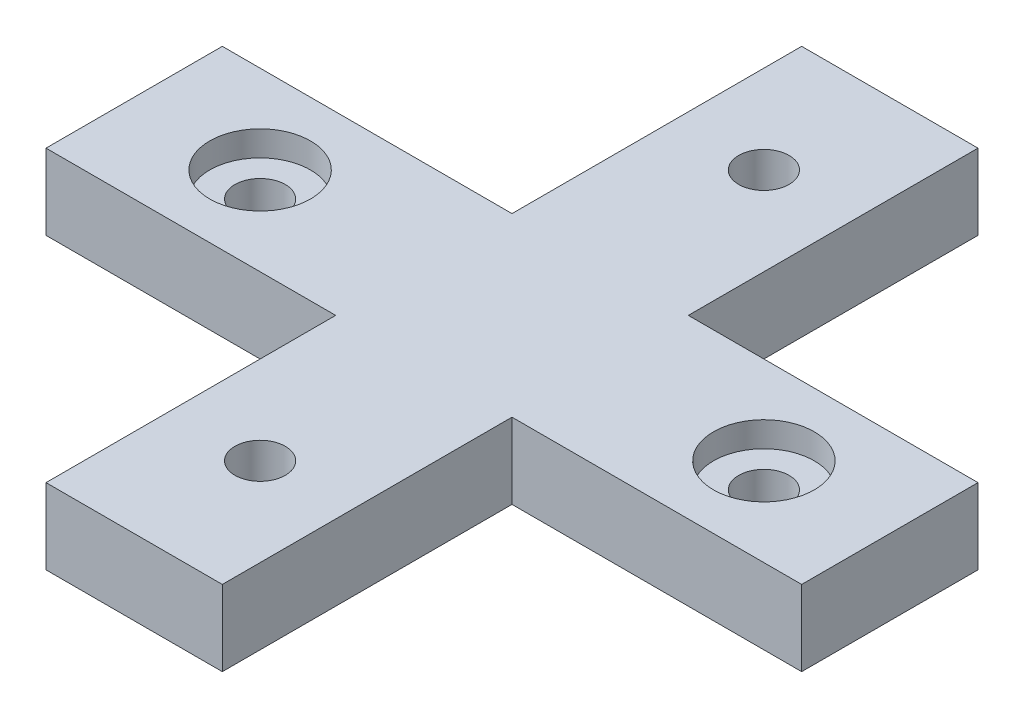
SolidWorks part; units mm, degrees
ref_plane "Front Plane" through (0, 0, 0) normal (0, 0, 1) x (1, 0, 0)
ref_plane "Top Plane" through (0, 0, 0) normal (0, 1, 0) x (1, 0, 0)
ref_plane "Right Plane" through (0, 0, 0) normal (1, 0, 0) x (0, 0, -1)
sketch "Sketch1" plane through (0, 0, 0) normal (0, 1, 0) x (1, 0, 0)
  line L1 (-15, 3.5) -> (15, 3.5)
  line L2 (-15, 3.5) -> (-15, -3.5)
  line L3 (-15, -3.5) -> (15, -3.5)
  line L4 (15, 3.5) -> (15, -3.5)
  line L5 (-15, 3.5) -> (15, -3.5) construction
  line L6 (-15, -3.5) -> (15, 3.5) construction
  line L7 (-3.5, 15) -> (3.5, 15)
  line L8 (-3.5, 15) -> (-3.5, -15)
  line L9 (-3.5, -15) -> (3.5, -15)
  line L10 (3.5, 15) -> (3.5, -15)
  line L11 (-3.5, 15) -> (3.5, -15) construction
  line L12 (-3.5, -15) -> (3.5, 15) construction
  circle A0 centre (0, 0) radius 1 construction
  circle A1 centre (0, 0) radius 2 construction
  circle A2 centre (10, 0) radius 1
  circle A3 centre (10, 0) radius 2
  circle A4 centre (-10, 0) radius 1
  circle A5 centre (-10, 0) radius 2
  circle A6 centre (0, 10) radius 1
  circle A7 centre (0, 10) radius 2
  circle A8 centre (0, -10) radius 1
  circle A9 centre (0, -10) radius 2
  dimension "D1" = 2
  dimension "D2" = 1
  dimension "D3" = 2
  dimension "D4" = 2
extrude "Boss-Extrude1" add sketch "Sketch1" along normal blind 3 contours L8 L1 L2 L3 A5 | L10 L1 L8 L3 | L1 L10 L3 L4 A3 | L10 L7 L8 L1 A7 | L10 L3 L8 L9 A9 | A7 A6 | A9 A8 region at (-9.25, 0, -3.3654) region at (-3.3654, 0, -9.25) region at (0, 0, 0) region at (9.25, 0, -3.3654) region at (0, 0, 3.6346) region at (-1.9434, 0, -10) region at (-1.9434, 0, 10)
extrude "Boss-Extrude2" add sketch "Sketch1<3>" along normal blind 2 contours A5 A4 | A3 A2 region at (8.0566, 0, 0) region at (-11.9434, 0, 0)
sketch "Sketch1<3>" plane through (0, 0, 0) normal (0, 1, 0) x (1, 0, 0) same geometry as "Sketch1"
